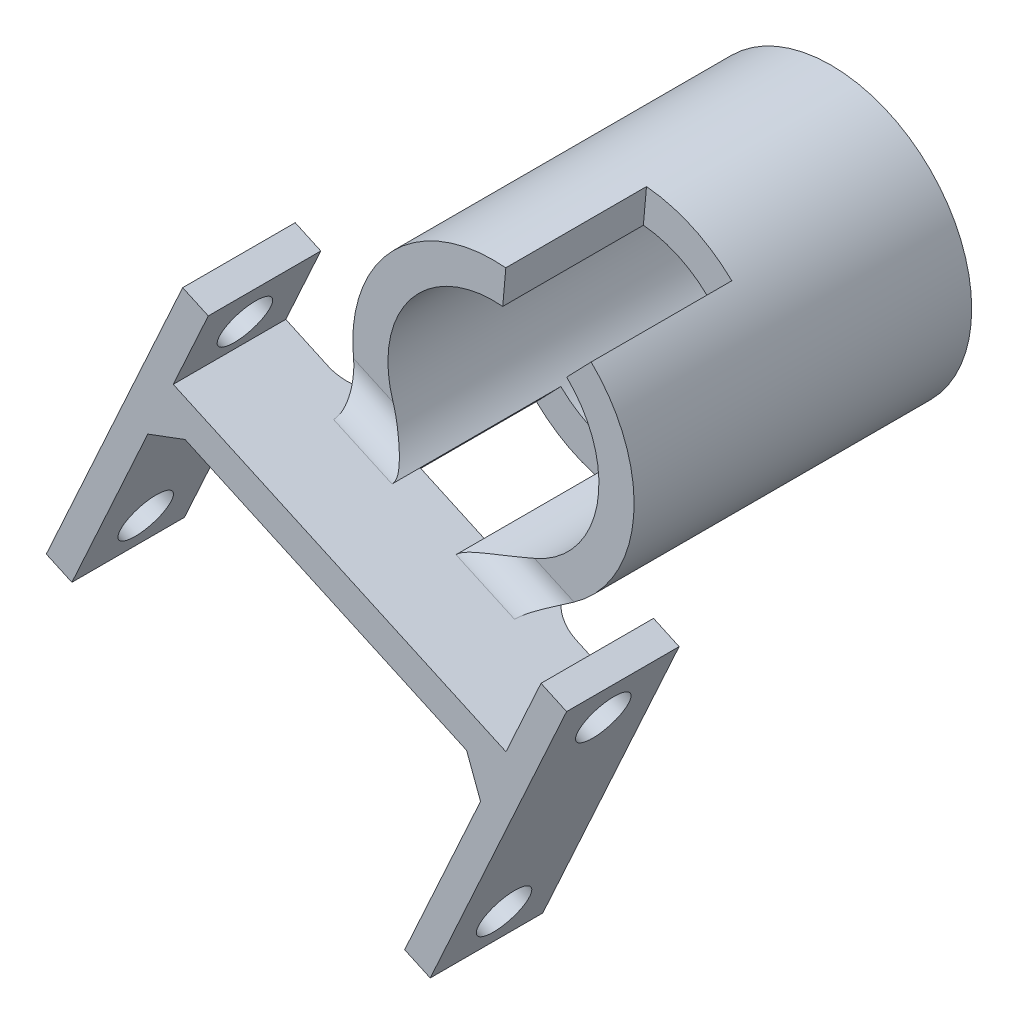
SolidWorks part; units mm, degrees
ref_plane "Front Plane" through (0, 0, 0) normal (0, 0, 1) x (1, 0, 0)
ref_plane "Top Plane" through (0, 0, 0) normal (0, 1, 0) x (1, 0, 0)
ref_plane "Right Plane" through (0, 0, 0) normal (1, 0, 0) x (0, 0, -1)
sketch "Sketch1" plane through (0, 0, 0) normal (0, 0, 1) x (1, 0, 0)
  circle A0 centre (0, 0) radius 3.285
  circle A1 centre (0, 0) radius 10
  circle A2 centre (0, 0) radius 7.5
  dimension "D1" = 6.57
  dimension "D2" = 20
  dimension "D3" = 15
extrude "Boss-Extrude1" add sketch "Sketch1" along normal blind 2 contours A2 A0 region at (-7.2879, 0, 0)
extrude "Boss-Extrude2" add sketch "Sketch1<3>" along normal blind 14 contours A1 A2 region at (-9.7172, 0, 0)
sketch "Sketch1<3>" plane through (0, 0, 0) normal (0, 0, 1) x (1, 0, 0) same geometry as "Sketch1"
sketch "Sketch2" plane through (0, 0, 14) normal (0, 0, 1) x (1, 0, 0)
  line L0 (-6.946, -7.194) -> (-5.2095, -5.3955)
  line L1 (5.2095, 5.3955) -> (6.946, 7.194)
  line L2 (0.6605, 7.4709) -> (0.8807, 9.9611)
  line L3 (-0.6605, -7.4709) -> (-0.8807, -9.9611)
  line L4 (0.6605, 7.4709) -> (5.2095, 5.3955) construction
  line L5 (-5.2095, -5.3955) -> (-0.6605, -7.4709) construction
  circle A0 centre (0, 0) radius 10 construction
  circle A1 centre (0, 0) radius 7.5 construction
  circle A2 centre (0, 0) radius 10
  circle A3 centre (0, 0) radius 7.5
  circle M1 centre (0, 0) radius 7.5
  circle M2 centre (0, 0) radius 10
  dimension "D1" = 5
  dimension "D2" = 5
extrude "Boss-Extrude3" add sketch "Sketch2" along normal blind 10 contours L2 L0 M1 M2 | L3 L1 M1 M2 region at (-8.9128, 4.0663, 14) region at (-0.5679, -8.7339, 14)
sketch "Sketch3" plane through (0, 0, 24) normal (0, 0, 1) x (1, 0, 0)
  line L0 (-4.1646, -8.4629) -> (-10.2298, -5.6958) construction
  line L2 (-0.6605, -7.4709) -> (-45490.0559, 20746.2014) construction
  line L3 (10.7118, -12.6593) -> (9.7335, -14.8037)
  line L4 (-16.5818, -0.2071) -> (-17.5602, -2.3515)
  line L5 (-16.5818, -0.2071) -> (10.7118, -12.6593)
  line L6 (9.7335, -14.8037) -> (-17.5602, -2.3515)
  dimension "D1" = 12.5
  dimension "D2" = 12.5
extrude "Boss-Extrude4" add sketch "Sketch3" along normal blind 8
fillet "Fillet1" radius 2 2 edges at (-7.2888, -4.4468, 24) (1.4188, -8.4195, 24)
fillet "Fillet2" radius 2 2 edges at (1.3419, -9.9096, 24) (-8.3638, -5.4815, 24)
sketch "Sketch4" plane through (-3.9133, -8.5776, 0) normal (-0.4151, -0.9098, 0) x (0.9098, -0.4151, 0)
  line L0 (-15, 24) -> (-7.4237, 24) construction
  line L1 (-15, 32) -> (-13, 32)
  line L2 (-15, 32) -> (-15, 24)
  line L3 (-15, 24) -> (-13, 24)
  line L4 (-13, 32) -> (-13, 24)
  line L5 (-15, 32) -> (15, 32) construction
  line L6 (15, 24) -> (13, 24)
  line L7 (15, 24) -> (15, 32)
  line L8 (15, 32) -> (13, 32)
  line L9 (13, 24) -> (13, 32)
  dimension "D1" = 2
  dimension "D2" = 2
extrude "Boss-Extrude5" add sketch "Sketch4" along normal blind 15
chamfer "Chamfer1" distance 2 angle 45 2 edges at (-15.7406, -3.1816, 28) (7.9139, -13.9735, 28)
sketch "Sketch6" plane through (-13.6468, 6.2261, 0) normal (-0.9098, 0.4151, 0) x (0, 0, 1)
  line L0 (32, -24.4281) -> (24, -24.4281) construction
  line L1 (24, -7.0711) -> (24, -24.4281) construction
  circle A0 centre (28, -21.4281) radius 1.825
  dimension "D1" = 3.65
  dimension "D2" = 3
  dimension "D3" = 4
extrude "Cut-Extrude1" cut sketch "Sketch6" against normal up to surface (30 mm away) up to face at (7.1096, -20.5549, 28)
sketch "Sketch7" plane through (-2.935, -6.4332, 0) normal (0.4151, 0.9098, 0) x (0.9098, -0.4151, 0)
  line L0 (15, -24) -> (9.6954, -24) construction
  line L1 (15, -32) -> (13, -32)
  line L2 (15, -32) -> (15, -24)
  line L3 (15, -24) -> (13, -24)
  line L4 (13, -32) -> (13, -24)
  line L5 (-9.6954, -24) -> (-15, -24) construction
  line L6 (-15, -32) -> (-13, -32)
  line L7 (-15, -32) -> (-15, -24)
  line L8 (-15, -24) -> (-13, -24)
  line L9 (-13, -32) -> (-13, -24)
  dimension "D1" = 2
  dimension "D2" = 2
extrude "Boss-Extrude6" add sketch "Sketch7" along normal blind 6
sketch "Sketch8" plane through (-13.6468, 6.2261, 0) normal (-0.9098, 0.4151, 0) x (0, 0, 1)
  line L0 (28, -1.0711) -> (28, -24.4281) construction
  line L1 (24, -1.0711) -> (32, -1.0711) construction
  line L2 (32, -24.4281) -> (24, -24.4281) construction
  circle A0 centre (28, -4.4281) radius 1.825
  circle A3 centre (28, -21.4281) radius 1.825 construction
  dimension "D2" = 3.65
  dimension "D1" = 17
extrude "Cut-Extrude2" cut sketch "Sketch8" against normal up to surface (30 mm away) up to face at (3.9951, -27.3815, 28)
